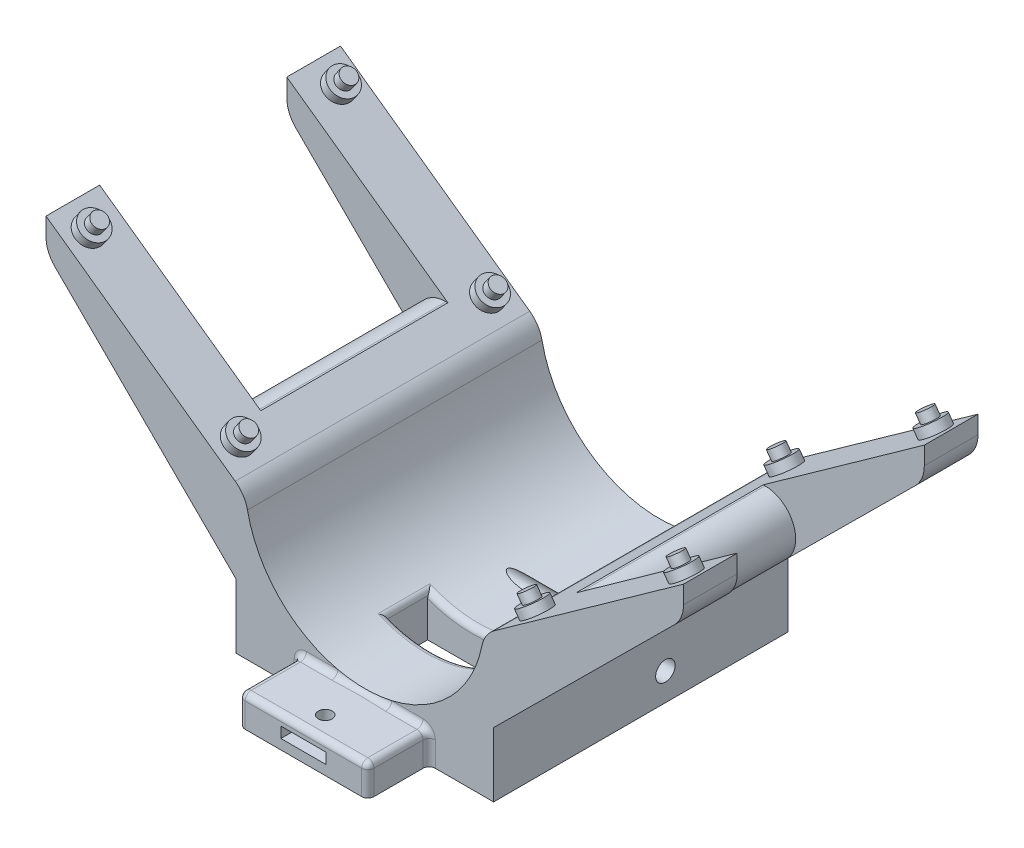
SolidWorks part; units mm, degrees
ref_plane "Front Plane" through (0, 0, 0) normal (0, 0, 1) x (1, 0, 0)
ref_plane "Top Plane" through (0, 0, 0) normal (0, 1, 0) x (1, 0, 0)
ref_plane "Right Plane" through (0, 0, 0) normal (1, 0, 0) x (0, 0, -1)
sketch "Sketch1" plane through (0, 0, 0) normal (0, 0, 1) x (1, 0, 0)
  line L0 (0, 0) -> (0, 23.1389) construction
  line L1 (-42, 0) -> (42, 0)
  line L3 (103.9203, 82.4609) -> (103.9203, 92.4609)
  line L4 (0, 50) -> (116.1922, 50) construction
  line L5 (103.9203, 92.4609) -> (38.7943, 46)
  line L9 (42, 0) -> (42, 21)
  line L10 (42, 21) -> (103.9203, 82.4609)
  line L11 (-42, 0) -> (-42, 21)
  line L12 (-42, 21) -> (-103.9203, 82.4609)
  line L13 (-103.9203, 82.4609) -> (-103.9203, 92.4609)
  line L14 (-103.9203, 92.4609) -> (-38.7943, 46)
  arc A0 (-38.7943, 46) -> (38.7943, 46) centre (0, 50) ccw
  point P11 (0, 0)
  dimension "D1" = 42
  dimension "D3" = 39
  dimension "D2" = 21
  dimension "D4" = 4
  dimension "D5" = 10
  dimension "D6" = 80
  dimension "D7" = 92.4609
extrude "Boss-Extrude1" add sketch "Sketch1" against normal mid plane 96
sketch "Sketch2" plane through (0, 0, 0) normal (1, 0, 0) x (0, 0, -1)
  line L1 (0, 0) -> (0, 25.8818) construction
  line L2 (-30.5, 92.4609) -> (30.5, 92.4609)
  line L3 (-30.5, 92.4609) -> (-30.5, 55)
  line L4 (-30.5, 55) -> (30.5, 55)
  line L5 (30.5, 92.4609) -> (30.5, 55)
  line L6 (-30.5, 92.4609) -> (30.5, 55) construction
  line L7 (-30.5, 55) -> (30.5, 92.4609) construction
  line L8 (48, 92.4609) -> (-48, 92.4609) construction
  line L9 (48, 0) -> (48, 21) construction
  circle A0 centre (8, 9) radius 3.175
  point P2 (0, 0)
  point P4 (0, 73.7304)
  dimension "D1" = 9
  dimension "D2" = 6.35
  dimension "D4" = 40
  dimension "D3" = 55
  dimension "D5" = 61
extrude "Cut-Extrude2" cut sketch "Sketch2" against normal up to next and the other way up to next contours L5 L2 L3 L4 | A0 region at (0, 73.7304, 0)
sketch "Sketch4" plane through (0, 0, 0) normal (0, 1, 0) x (1, 0, 0)
  line L0 (38.7943, 48) -> (-38.7943, 48) construction
  line L1 (-14.5, -26) -> (14.5, -26)
  line L2 (-14.5, -26) -> (-14.5, -13)
  line L3 (-14.5, -13) -> (14.5, -13)
  line L4 (14.5, -26) -> (14.5, -13)
  line L5 (-14.5, -26) -> (14.5, -13) construction
  line L6 (-14.5, -13) -> (14.5, -26) construction
  line L8 (0, 0) -> (0, -28.6341) construction
  point P0 (0, -19.5)
  point P14 (0, 0)
  point P21 (0, 0)
  dimension "D1" = 61
  dimension "D2" = 13
  dimension "D3" = 29
extrude "Cut-Extrude3" cut sketch "Sketch4" along normal up to next
sketch "Sketch5" plane through (0, 0, 48) normal (0, 0, 1) x (1, 0, 0)
  line L1 (-21, 10) -> (21, 10)
  line L2 (-21, 10) -> (-21, 0)
  line L3 (-21, 0) -> (21, 0)
  line L4 (21, 10) -> (21, 0)
  line L5 (-21, 10) -> (21, 0) construction
  line L6 (-21, 0) -> (21, 10) construction
  line L7 (-42, 0) -> (42, 0) construction
  line L8 (0, -1000) -> (0, 49000) construction
  line L10 (-7.35, 6.75) -> (7.35, 6.75)
  line L11 (-7.35, 6.75) -> (-7.35, 3.25)
  line L12 (-7.35, 3.25) -> (7.35, 3.25)
  line L13 (7.35, 6.75) -> (7.35, 3.25)
  line L14 (-7.35, 6.75) -> (7.35, 3.25) construction
  line L15 (-7.35, 3.25) -> (7.35, 6.75) construction
  point P0 (0, 5)
  point P5 (0, 5)
  dimension "D1" = 10
  dimension "D2" = 42
  dimension "D3" = 3.5
extrude "Boss-Extrude2" add sketch "Sketch5" along normal blind 20
sketch "Sketch6" plane through (0, 10, 0) normal (0, 1, 0) x (1, 0, 0)
  line L0 (0, 0) -> (0, -16.9975) construction
  circle A0 centre (0, -60.8854) radius 2.25
  point P3 (0, 0)
extrude "Cut-Extrude4" cut sketch "Sketch6" against normal through all
fillet "Fillet1" radius 10 8 edges at (103.9203, 82.4609, -39.25) (103.9203, 82.4609, 39.25) (76.2541, 55, 0) (-103.9203, 82.4609, 39.25) (-103.9203, 82.4609, -39.25) (-76.2541, 55, 0) (-38.7943, 46, 0) (38.7943, 46, 0)
fillet "Fillet2" radius 2 4 edges at (14.5, 13.7957, 19.5) (0, 11, 13) (0, 11, 26) (-14.5, 13.7957, 19.5)
fillet "Fillet4" radius 2 8 edges at (21, 5, 48) (21, 5, 68) (21, 10, 58) (-21, 10, 58) (0, 10, 68) (-21, 5, 68) (0, 10, 48) (-21, 5, 48)
sketch "Sketch7" plane through (-8.6633, 12.1437, 0) normal (-0.5808, 0.8141, 0) x (0.8141, 0.5808, 0)
  line L1 (73.7934, -30.5) -> (138.2965, -30.5) construction
  line L2 (138.2965, -30.5) -> (138.2965, -48) construction
  line L3 (138.2965, -48) -> (62.5093, -48) construction
  line L4 (138.2965, 48) -> (138.2965, 30.5) construction
  circle A1 centre (130.2965, -40.5) radius 4.5
  circle A2 centre (70.6065, -40.5) radius 4.5
  circle A3 centre (130.2965, 40.78) radius 4.5
  circle A4 centre (70.6065, 40.78) radius 4.5
  circle A5 centre (130.2965, -40.5) radius 2.5
  circle A6 centre (130.2965, 40.78) radius 2.5
  circle A7 centre (70.6065, -40.5) radius 2.5
  circle A8 centre (70.6065, 40.78) radius 2.5
  dimension "D1" = 10
  dimension "D2" = 8
  dimension "D3" = 59.69
  dimension "D4" = 7.5
  dimension "D5" = 81.28
  dimension "D6" = 8
  dimension "D7" = 59.69
  dimension "D8" = 81.28
extrude "Boss-Extrude3" add sketch "Sketch7" along normal blind 3
extrude "Boss-Extrude4" add sketch "Sketch7<3>" along normal blind 6 contours A7 | A8 | A6 | A5 region at (97.4077, 87.8148, -40.78) region at (48.8156, 53.1492, 40.5) region at (48.8156, 53.1492, -40.78)
sketch "Sketch7<3>" plane through (-8.6633, 12.1437, 0) normal (-0.5808, 0.8141, 0) x (0.8141, 0.5808, 0) same geometry as "Sketch7"
mirror "Mirror1" about plane through (0, 0, 0) normal (1, 0, 0) of "Boss-Extrude3", "Boss-Extrude4"
